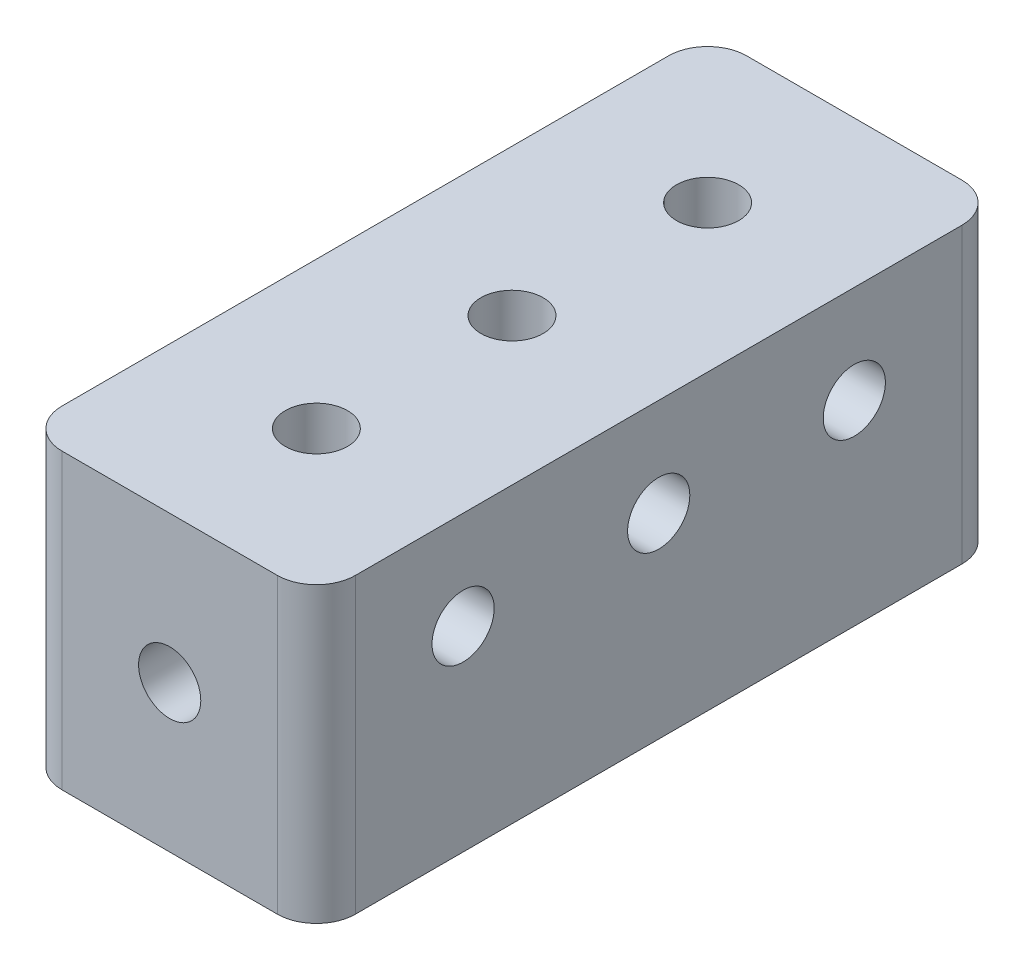
SolidWorks part; units mm, degrees
material "6061-T6 (SS)"
ref_plane "Front Plane" through (0, 0, 0) normal (0, 0, 1) x (1, 0, 0)
ref_plane "Top Plane" through (0, 0, 0) normal (0, 1, 0) x (1, 0, 0)
ref_plane "Right Plane" through (0, 0, 0) normal (1, 0, 0) x (0, 0, -1)
sketch "Sketch1" plane through (0, 0, 0) normal (0, 1, 0) x (1, 0, 0)
  line L1 (-9.525, -22.225) -> (9.525, -22.225)
  line L2 (-9.525, -22.225) -> (-9.525, 22.225)
  line L3 (-9.525, 22.225) -> (9.525, 22.225)
  line L4 (9.525, -22.225) -> (9.525, 22.225)
  line L5 (-9.525, -22.225) -> (9.525, 22.225) construction
  line L6 (-9.525, 22.225) -> (9.525, -22.225) construction
  point P0 (0, 0)
  dimension "D1" = 19.05
  dimension "D2" = 44.45
extrude "Boss-Extrude1" add sketch "Sketch1" along normal mid plane 19.05
sketch "Sketch2" plane through (0, 0, 22.225) normal (0, 0, 1) x (1, 0, 0)
  circle A0 centre (0, 0) radius 2.0193
  dimension "D3" = 4.0386
extrude "Cut-Extrude1" cut sketch "Sketch2" against normal blind 9.525
sketch "Sketch3" plane through (0, 0, -22.225) normal (0, 0, -1) x (-1, 0, 0)
  circle A0 centre (0, 0) radius 2.0193 construction
  circle A1 centre (0, 0) radius 2.0193
extrude "Cut-Extrude2" cut sketch "Sketch3" against normal blind 9.525
sketch "Sketch4" plane through (9.525, 0, 0) normal (1, 0, 0) x (0, 0, -1)
  line L0 (-22.225, 9.525) -> (22.225, 9.525) construction
  circle A0 centre (-12.7, 3.175) radius 2.0193
  circle A1 centre (12.7, 3.175) radius 2.0193
  circle A2 centre (0, 3.175) radius 2.0193
  dimension "D5" = 4.0386
  dimension "D1" = 6.35
  dimension "D3" = 12.7
  dimension "D4" = 12.7
extrude "Cut-Extrude3" cut sketch "Sketch4" against normal blind 6.35
sketch "Sketch5" plane through (-9.525, 0, 0) normal (-1, 0, 0) x (0, 0, 1)
  circle A0 centre (-12.7, 3.175) radius 2.0193 construction
  circle A1 centre (0, 3.175) radius 2.0193 construction
  circle A2 centre (12.7, 3.175) radius 2.0193 construction
  circle A3 centre (-12.7, 3.175) radius 2.0193
  circle A4 centre (0, 3.175) radius 2.0193
  circle A5 centre (12.7, 3.175) radius 2.0193
extrude "Cut-Extrude4" cut sketch "Sketch5" against normal blind 6.35
sketch "Sketch6" plane through (0, 9.525, 0) normal (0, 1, 0) x (1, 0, 0)
  circle A0 centre (0, 12.7) radius 2.0193
  circle A1 centre (0, 0) radius 2.0193
  circle A2 centre (0, -12.7) radius 2.0193
  point P6 (0, 0)
  dimension "D1" = 4.0386
  dimension "D2" = 12.7
  dimension "D3" = 12.7
extrude "Cut-Extrude5" cut sketch "Sketch6" against normal blind 6.35
fillet "Fillet1" radius 2.54 4 edges at (9.525, 0, 22.225) (-9.525, 0, 22.225) (-9.525, 0, -22.225) (9.525, 0, -22.225)
